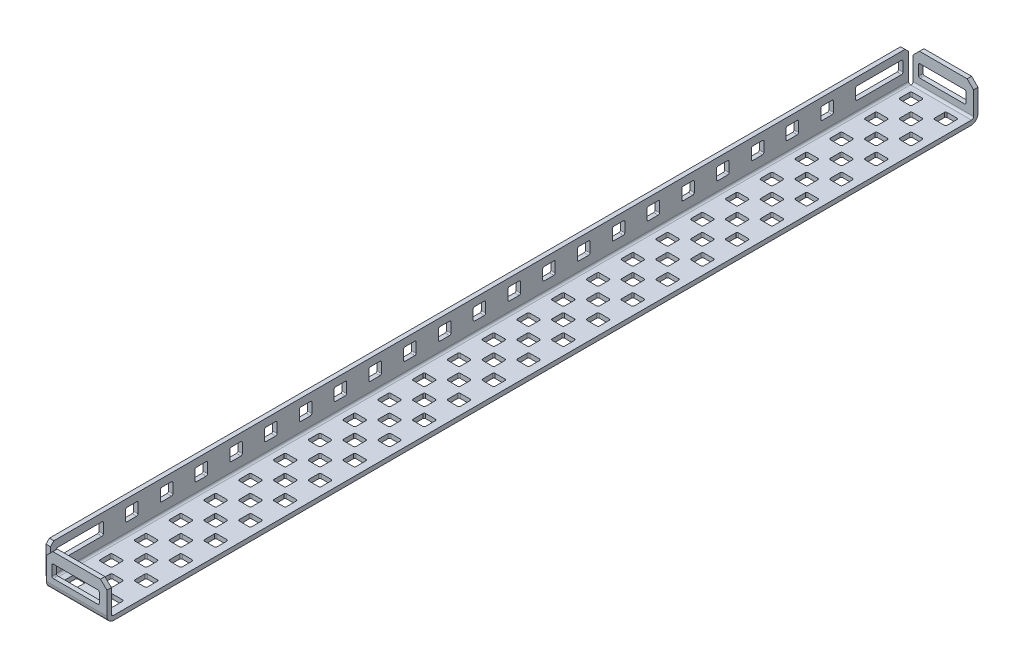
SolidWorks part; units mm, degrees
material "5052-H32"
ref_plane "Front Plane" through (0, 0, 0) normal (0, 0, 1) x (1, 0, 0)
ref_plane "Top Plane" through (0, 0, 0) normal (0, 1, 0) x (1, 0, 0)
ref_plane "Right Plane" through (0, 0, 0) normal (1, 0, 0) x (0, 0, -1)
sketch "Sketch1" plane through (0, 0, 0) normal (0, 0, 1) x (1, 0, 0)
  line L0 (0, 0) -> (-22.098, 0)
  line L1 (-24.638, 2.54) -> (-24.638, 13.1318)
  line L2 (-24.638, 13.1318) -> (-23.0124, 13.1318)
  line L3 (0, 0) -> (0, 1.6256)
  line L4 (-23.0124, 13.1318) -> (-23.0124, 2.3876)
  line L5 (-22.2504, 1.6256) -> (0, 1.6256)
  arc A0 (-22.098, 0) -> (-24.638, 2.54) centre (-22.098, 2.54) cw
  arc A1 (-23.0124, 2.3876) -> (-22.2504, 1.6256) centre (-22.2504, 2.3876) ccw
  dimension "D3" = 2.54
  dimension "D6" = 0.762
  dimension "D1" = 1.6256
  dimension "D2" = 1.6256
  dimension "D4" = 24.638
  dimension "D5" = 13.1318
extrude "Boss-Extrude1" add sketch "Sketch1" against normal blind 313.436
sketch "Sketch3" plane through (-24.638, 0, 0) normal (-1, 0, 0) x (0, 0, 1)
  line L0 (-313.436, 13.1318) -> (0, 13.1318) construction
  line L1 (-2.54, 10.3378) -> (-18.796, 10.3378)
  line L2 (-2.032, 9.8298) -> (-2.032, 6.2738)
  line L3 (-2.54, 5.7658) -> (-18.796, 5.7658)
  line L4 (-19.304, 9.8298) -> (-19.304, 6.2738)
  line L5 (0, 13.1318) -> (0, 2.54) construction
  line L6 (-1.2572, 13.1318) -> (0, 11.8746)
  line L7 (-1.2572, 13.1318) -> (0, 13.1318)
  line L8 (0, 13.1318) -> (0, 11.8746)
  line L9 (-156.718, 20.1457) -> (-156.718, -6.2552) construction
  line L10 (-313.436, 13.1318) -> (-313.436, 11.8746)
  line L11 (-312.1788, 13.1318) -> (-313.436, 13.1318)
  line L12 (-312.1788, 13.1318) -> (-313.436, 11.8746)
  line L13 (-310.896, 10.3378) -> (-294.64, 10.3378)
  line L14 (-311.404, 9.8298) -> (-311.404, 6.2738)
  line L15 (-310.896, 5.7658) -> (-294.64, 5.7658)
  line L16 (-294.132, 9.8298) -> (-294.132, 6.2738)
  arc A0 (-18.796, 5.7658) -> (-19.304, 6.2738) centre (-18.796, 6.2738) cw
  arc A1 (-2.032, 6.2738) -> (-2.54, 5.7658) centre (-2.54, 6.2738) cw
  arc A2 (-2.54, 10.3378) -> (-2.032, 9.8298) centre (-2.54, 9.8298) cw
  arc A3 (-18.796, 10.3378) -> (-19.304, 9.8298) centre (-18.796, 9.8298) ccw
  arc A4 (-310.896, 10.3378) -> (-311.404, 9.8298) centre (-310.896, 9.8298) ccw
  arc A5 (-311.404, 6.2738) -> (-310.896, 5.7658) centre (-310.896, 6.2738) ccw
  arc A6 (-294.64, 5.7658) -> (-294.132, 6.2738) centre (-294.64, 6.2738) ccw
  arc A7 (-294.64, 10.3378) -> (-294.132, 9.8298) centre (-294.64, 9.8298) cw
  point P14 (-156.718, 13.1318)
  point P17 (-19.304, 5.7658)
  point P20 (-2.032, 5.7658)
  point P25 (-19.304, 10.3378)
  dimension "D7" = 0.508
  dimension "D1" = 4.572
  dimension "D2" = 17.272
  dimension "D3" = 2.794
  dimension "D4" = 2.032
  dimension "D5" = 1.778
  dimension "D6" = 45
extrude "Cut-Extrude1" cut sketch "Sketch3" against normal through all
sketch "Sketch4" plane through (-24.638, 0, 0) normal (-1, 0, 0) x (0, 0, 1)
  line L0 (-27.94, 10.3378) -> (-31.496, 10.3378)
  line L1 (-32.004, 9.8298) -> (-32.004, 6.2738)
  line L2 (-31.496, 5.7658) -> (-27.94, 5.7658)
  line L3 (-27.432, 6.2738) -> (-27.432, 9.8298)
  line L4 (-18.796, 5.7658) -> (-2.54, 5.7658) construction
  line L5 (-2.54, 10.3378) -> (-18.796, 10.3378) construction
  line L6 (-19.304, 9.8298) -> (-19.304, 6.2738) construction
  arc A0 (-27.94, 10.3378) -> (-27.432, 9.8298) centre (-27.94, 9.8298) cw
  arc A1 (-27.94, 5.7658) -> (-27.432, 6.2738) centre (-27.94, 6.2738) ccw
  arc A2 (-32.004, 6.2738) -> (-31.496, 5.7658) centre (-31.496, 6.2738) ccw
  arc A3 (-31.496, 10.3378) -> (-32.004, 9.8298) centre (-31.496, 9.8298) ccw
  dimension "D1" = 0.508
  dimension "D2" = 8.128
extrude "Cut-Extrude2" cut sketch "Sketch4" against normal through all
pattern_linear "LPattern1" count 21 spacing 12.7 along (0, 0, -1) of "Cut-Extrude2"
sketch "Sketch5" plane through (0, 1.6256, 0) normal (0, 1, 0) x (1, 0, 0)
  line L0 (0, 0) -> (-22.2504, 0) construction
  line L1 (-3.302, 2.032) -> (-6.858, 2.032)
  line L2 (-2.794, 2.54) -> (-2.794, 6.096)
  line L3 (-3.302, 6.604) -> (-6.858, 6.604)
  line L4 (-7.366, 2.54) -> (-7.366, 6.096)
  line L6 (0, 313.436) -> (0, 0) construction
  arc A0 (-6.858, 2.032) -> (-7.366, 2.54) centre (-6.858, 2.54) cw
  arc A1 (-3.302, 2.032) -> (-2.794, 2.54) centre (-3.302, 2.54) ccw
  arc A2 (-2.794, 6.096) -> (-3.302, 6.604) centre (-3.302, 6.096) ccw
  arc A3 (-6.858, 6.604) -> (-7.366, 6.096) centre (-6.858, 6.096) ccw
  point P10 (-7.366, 2.032)
  point P15 (-2.794, 6.604)
  point P18 (-7.366, 6.604)
  dimension "D5" = 0.508
  dimension "D1" = 4.572
  dimension "D2" = 4.572
  dimension "D3" = 2.032
  dimension "D4" = 2.794
extrude "Cut-Extrude3" cut sketch "Sketch5" against normal through all
pattern_linear "LPattern2" count 2 spacing 12.7 along (-1, 0, 0) count 25 spacing 12.7 along (0, 0, -1) of "Cut-Extrude3"
sketch "Sketch6" plane through (0, 1.6256, 0) normal (0, 1, 0) x (1, 0, 0)
  line L1 (-13.208, 12.954) -> (-9.652, 12.954)
  line L2 (-13.716, 12.446) -> (-13.716, 8.89)
  line L3 (-13.208, 8.382) -> (-9.652, 8.382)
  line L4 (-9.144, 12.446) -> (-9.144, 8.89)
  line L8 (-3.302, 6.604) -> (-6.858, 6.604) construction
  line L9 (-7.366, 18.796) -> (-7.366, 15.24) construction
  arc A4 (-9.652, 12.954) -> (-9.144, 12.446) centre (-9.652, 12.446) cw
  arc A5 (-9.652, 8.382) -> (-9.144, 8.89) centre (-9.652, 8.89) ccw
  arc A6 (-13.716, 8.89) -> (-13.208, 8.382) centre (-13.208, 8.89) ccw
  arc A7 (-13.208, 12.954) -> (-13.716, 12.446) centre (-13.208, 12.446) ccw
  point P12 (-9.144, 8.382)
  point P15 (-13.716, 8.382)
  point P18 (-13.716, 12.954)
  dimension "D5" = 0.508
  dimension "D1" = 4.572
  dimension "D2" = 4.572
  dimension "D3" = 1.778
  dimension "D4" = 1.778
extrude "Cut-Extrude4" cut sketch "Sketch6" against normal through all
pattern_linear "LPattern3" count 24 spacing 12.7 along (0, 0, -1) of "Cut-Extrude4"
sketch "Sketch7" plane through (0, 0, 0) normal (1, 0, 0) x (0, 0, -1)
  line L0 (0, 0) -> (0, 1.6256)
  line L1 (-0.762, 2.3876) -> (-0.762, 13.1318)
  line L2 (-0.762, 13.1318) -> (-2.3876, 13.1318)
  line L3 (-2.3876, 13.1318) -> (-2.3876, 2.5354)
  line L5 (313.436, 0) -> (0, 0) construction
  line L6 (156.718, 16.3537) -> (156.718, -4.4019) construction
  line L7 (314.198, 2.3876) -> (314.198, 13.1318)
  line L8 (314.198, 13.1318) -> (315.8236, 13.1318)
  line L9 (315.8236, 13.1318) -> (315.8236, 2.5354)
  line L10 (313.436, 0) -> (313.436, 1.6256)
  arc A0 (0, 1.6256) -> (-0.762, 2.3876) centre (0, 2.3876) cw
  arc A1 (-2.3876, 2.5354) -> (0, 0) centre (0.1524, 2.5354) ccw
  arc A2 (313.436, 1.6256) -> (314.198, 2.3876) centre (313.436, 2.3876) ccw
  arc A3 (315.8236, 2.5354) -> (313.436, 0) centre (313.2836, 2.5354) cw
  dimension "D1" = 2.54
  dimension "D2" = 0.762
  dimension "D3" = 1.6256
  dimension "D4" = 13.1318
  dimension "D5" = 156.718
extrude "Boss-Extrude2" add sketch "Sketch7" against normal blind 22.098
sketch "Sketch8" plane through (0, 0, 2.3876) normal (0, 0, 1) x (1, 0, 0)
  line L0 (0, 13.1318) -> (0, 2.5354) construction
  line L1 (-19.558, 9.2711) -> (-3.302, 9.2711)
  line L2 (-20.066, 8.7631) -> (-20.066, 5.2071)
  line L3 (-19.558, 4.6991) -> (-3.302, 4.6991)
  line L4 (-2.794, 8.7631) -> (-2.794, 5.2071)
  line L5 (-22.098, 13.1318) -> (-22.098, 2.5354) construction
  line L6 (-22.098, 10.7969) -> (-19.7631, 13.1318)
  line L7 (-22.098, 13.1318) -> (0, 13.1318) construction
  line L8 (-11.049, 15.2374) -> (-11.049, -3.094) construction
  line L9 (-22.098, 10.7969) -> (-22.098, 13.1318)
  line L10 (-22.098, 13.1318) -> (-19.7631, 13.1318)
  line L11 (0, 10.7969) -> (-2.3349, 13.1318)
  line L12 (0, 13.1318) -> (-2.3349, 13.1318)
  line L13 (0, 10.7969) -> (0, 13.1318)
  arc A0 (-20.066, 5.2071) -> (-19.558, 4.6991) centre (-19.558, 5.2071) ccw
  arc A1 (-3.302, 4.6991) -> (-2.794, 5.2071) centre (-3.302, 5.2071) ccw
  arc A2 (-3.302, 9.2711) -> (-2.794, 8.7631) centre (-3.302, 8.7631) cw
  arc A3 (-19.558, 9.2711) -> (-20.066, 8.7631) centre (-19.558, 8.7631) ccw
  point P12 (-2.794, 4.6991)
  point P15 (-2.794, 9.2711)
  point P24 (-11.049, 13.1318)
  dimension "D4" = 0.508
  dimension "D1" = 4.572
  dimension "D2" = 2.794
  dimension "D3" = 2.032
  dimension "D5" = 3.302
  dimension "D6" = 45
extrude "Cut-Extrude5" cut sketch "Sketch8" against normal through all
